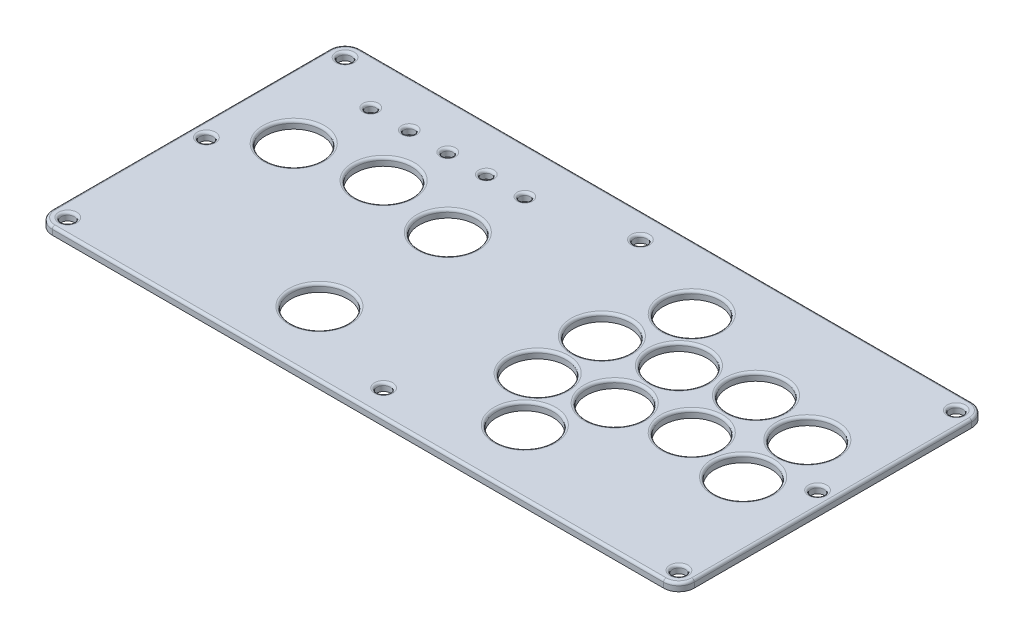
SolidWorks part; units mm, degrees
ref_plane "前视基准面" through (0, 0, 0) normal (0, 0, 1) x (1, 0, 0)
ref_plane "上视基准面" through (0, 0, 0) normal (0, 1, 0) x (1, 0, 0)
ref_plane "右视基准面" through (0, 0, 0) normal (1, 0, 0) x (0, 0, -1)
sketch "草图1" plane through (0, 0, 0) normal (0, 1, 0) x (1, 0, 0)
  line L0 (20.9031, 127.7613) -> (258.9031, 127.7613)
  line L1 (264.9031, 121.7613) -> (264.9031, 13.7613)
  line L2 (258.9031, 7.7613) -> (20.9031, 7.7613)
  line L3 (14.9031, 13.7613) -> (14.9031, 121.7613)
  arc A0 (20.9031, 127.7613) -> (14.9031, 121.7613) centre (20.9031, 121.7613) ccw
  arc A1 (264.9031, 121.7613) -> (258.9031, 127.7613) centre (258.9031, 121.7613) ccw
  arc A2 (258.9031, 7.7613) -> (264.9031, 13.7613) centre (258.9031, 13.7613) ccw
  arc A3 (14.9031, 13.7613) -> (20.9031, 7.7613) centre (20.9031, 13.7613) ccw
  circle A4 centre (20.9031, 121.7613) radius 2.55
  circle A5 centre (258.9031, 121.7613) radius 2.55
  circle A6 centre (139.9031, 117.7613) radius 2.55
  circle A7 centre (20.9031, 13.7613) radius 2.55
  circle A8 centre (258.9031, 13.7613) radius 2.55
  circle A9 centre (139.9031, 17.7613) radius 2.55
  circle A10 centre (258.9031, 67.7613) radius 2.55
  circle A11 centre (20.9031, 67.7613) radius 2.55
  circle A12 centre (164.9031, 77.7613) radius 11
  circle A13 centre (189.9031, 82.7613) radius 11
  circle A14 centre (214.9031, 87.7613) radius 11
  circle A15 centre (239.9031, 82.7613) radius 11
  circle A16 centre (164.9031, 52.7613) radius 11
  circle A17 centre (189.9031, 57.7613) radius 11
  circle A18 centre (214.9031, 62.7613) radius 11
  circle A19 centre (239.9031, 57.7613) radius 11
  circle A20 centre (174.9031, 102.7613) radius 11
  circle A21 centre (179.9031, 32.7613) radius 11
  circle A22 centre (99.9031, 82.7613) radius 11
  circle A23 centre (69.9031, 87.7613) radius 11
  circle A24 centre (39.9031, 82.7613) radius 11
  circle A25 centre (99.9031, 32.7613) radius 11
  circle B0 centre (42.9031, 109.7613) radius 2
  circle B1 centre (57.9031, 109.7613) radius 2
  circle B2 centre (72.9031, 109.7613) radius 2
  circle B3 centre (87.9031, 109.7613) radius 2
  circle B4 centre (102.9031, 109.7613) radius 2
  dimension "D3" = 22
  dimension "D1" = 250
  dimension "D2" = 120
sketch_block_instance "*U1-1"
sketch_block "*U1"
extrude "凸台-拉伸1" add sketch "草图1" along normal blind 3
fillet "圆角1" radius 1 35 edges at (102.9031, 3, -107.7613) (72.9031, 3, -107.7613) (42.9031, 3, -107.7613) (39.9031, 3, -71.7613) (99.9031, 3, -71.7613) (174.9031, 3, -91.7613) (214.9031, 3, -51.7613) (164.9031, 3, -41.7613) (214.9031, 3, -76.7613) (164.9031, 3, -66.7613) (258.9031, 3, -65.2113) (258.9031, 3, -11.2113) (139.9031, 3, -115.2113) (20.9031, 3, -119.2113) (139.9031, 3, -127.7613) (263.1458, 3, -126.004) (264.9031, 3, -67.7613) (263.1458, 3, -9.5187) (139.9031, 3, -7.7613) (16.6605, 3, -9.5187) (14.9031, 3, -67.7613) (16.6605, 3, -126.004) (258.9031, 3, -119.2113) (20.9031, 3, -11.2113) (139.9031, 3, -15.2113) (20.9031, 3, -65.2113) (189.9031, 3, -71.7613) (239.9031, 3, -71.7613) (189.9031, 3, -46.7613) (239.9031, 3, -46.7613) (179.9031, 3, -21.7613) (69.9031, 3, -76.7613) (99.9031, 3, -21.7613) (57.9031, 3, -107.7613) (87.9031, 3, -107.7613)
